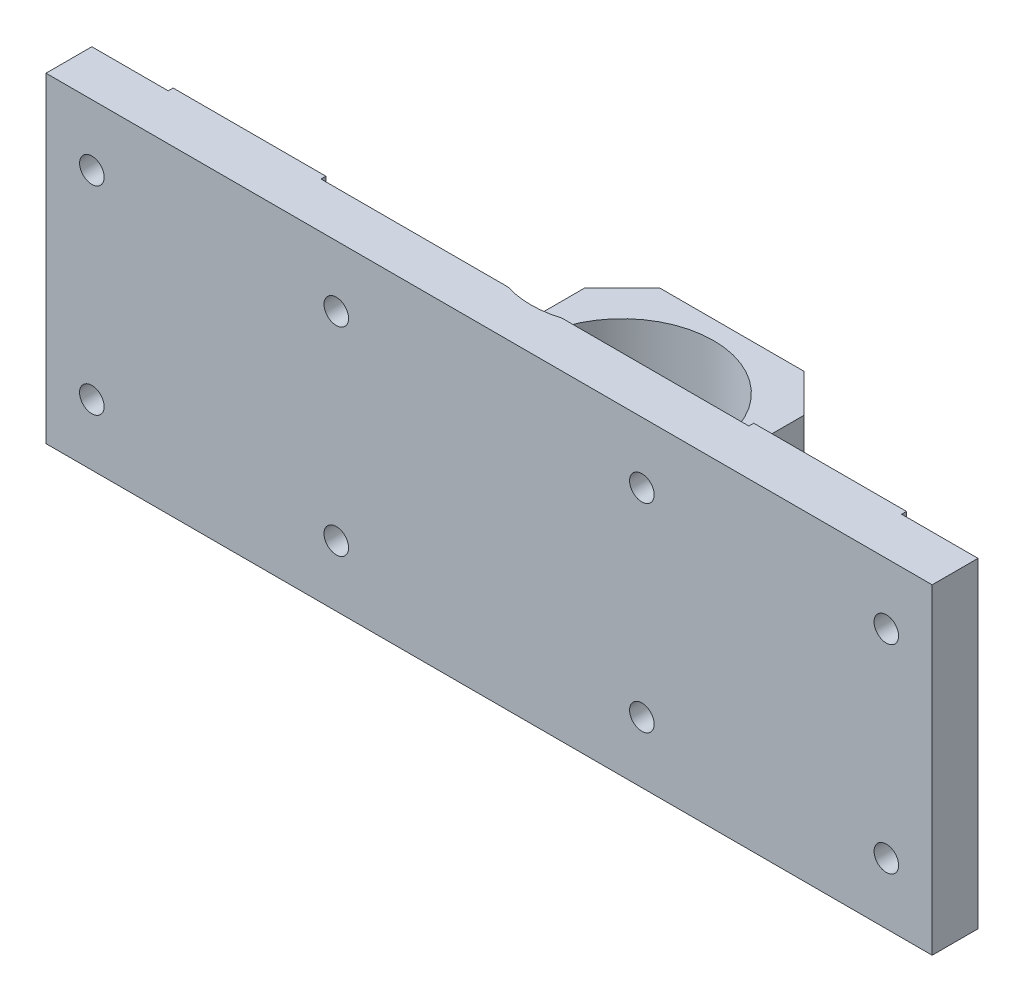
SolidWorks part; units mm, degrees
ref_plane "Front Plane" through (0, 0, 0) normal (0, 0, 1) x (1, 0, 0)
ref_plane "Top Plane" through (0, 0, 0) normal (0, 1, 0) x (1, 0, 0)
ref_plane "Right Plane" through (0, 0, 0) normal (1, 0, 0) x (0, 0, -1)
sketch "Sketch1" plane through (0, 0, 0) normal (0, 0, 1) x (1, 0, 0)
  line L1 (-87.7906, 37.622) -> (96.3594, 37.622)
  line L2 (-87.7906, 37.622) -> (-87.7906, -29.053)
  line L3 (-87.7906, -29.053) -> (96.3594, -29.053)
  line L4 (96.3594, 37.622) -> (96.3594, -29.053)
  dimension "D1" = 184.15
  dimension "D2" = 66.675
extrude "Boss-Extrude1" add sketch "Sketch1" along normal blind 9.525
sketch "Sketch5" plane through (0, 37.622, 0) normal (0, 1, 0) x (1, 0, 0)
  line L0 (10.8884, 0) -> (10.8884, -9.525)
  line L1 (96.3594, 0) -> (-87.7906, 0) construction
  line L2 (96.3594, -9.525) -> (-87.7906, -9.525) construction
  line L3 (-2.3196, 0) -> (-2.3196, -9.525)
  point P8 (4.2844, 0)
  dimension "D1" = 6.604
  dimension "D2" = 6.604
sketch "Sketch6" plane through (0, 37.622, 0) normal (0, 1, 0) x (1, 0, 0)
  arc A0 (10.8884, 0) -> (-2.3196, 0) centre (4.2844, 10.8827) cw
extrude "Cut-Extrude1" cut sketch "Sketch6" against normal through all and the other way through all flip side to cut
sketch "Sketch7" plane through (0, 37.622, 0) normal (0, 1, 0) x (1, 0, 0)
  line L0 (4.2844, -4.7215) -> (4.2844, 18.1385)
  line L1 (-87.7906, -9.525) -> (-87.7906, 0) construction
  circle A1 centre (4.2844, 18.1385) radius 22.8473
  dimension "D1" = 22.86
  dimension "D2" = 92.075
extrude "Boss-Extrude2" add sketch "Sketch7" against normal through all contours A1
sketch "Sketch8" plane through (0, 37.622, 0) normal (0, 1, 0) x (1, 0, 0)
  circle A0 centre (4.2844, 18.1385) radius 18.9865
  dimension "D1" = 37.973
extrude "Cut-Extrude2" cut sketch "Sketch8" against normal blind 61.595
sketch "Sketch9" plane through (0, -23.973, 0) normal (0, 1, 0) x (1, 0, 0)
  circle A0 centre (4.2844, 18.1385) radius 7.9375
  circle A1 centre (4.2844, 18.1385) radius 18.9865 construction
  dimension "D1" = 15.875
  dimension "D2" = 0
extrude "Cut-Extrude3" cut sketch "Sketch9" against normal through all
sketch "Sketch12" plane through (0, 37.622, 0) normal (0, 1, 0) x (1, 0, 0)
  line L0 (27.1317, 18.1385) -> (27.1317, 0)
  line L1 (96.3594, 0) -> (18.1766, 0) construction
  line L2 (27.1317, 0) -> (18.1766, 0)
  line L3 (-18.5629, 18.1385) -> (-18.5629, 0)
  line L4 (-9.6078, 0) -> (-87.7906, 0) construction
  line L5 (-18.5629, 0) -> (-9.6078, 0)
  circle A0 centre (4.2844, 18.1385) radius 22.8473 construction
  arc A1 (18.1766, 0) -> (27.1317, 18.1385) centre (4.2844, 18.1385) ccw
  arc A2 (-9.6078, 0) -> (-18.5629, 18.1385) centre (4.2844, 18.1385) cw
extrude "Boss-Extrude3" add sketch "Sketch12" against normal up to surface (66.675 mm away) up to face at (4.2844, -29.053, -10.201)
sketch "Sketch16" plane through (0, -29.053, 0) normal (0, -1, 0) x (1, 0, 0)
  line L0 (-18.5629, -18.1385) -> (-18.5629, -40.9857)
  line L1 (4.2844, -40.9857) -> (-18.5629, -40.9857)
  arc A0 (-18.5629, -18.1385) -> (27.1317, -18.1385) centre (4.2844, -18.1385) ccw construction
  arc A1 (-18.5629, -18.1385) -> (4.2844, -40.9857) centre (4.2844, -18.1385) ccw
extrude "Boss-Extrude4" add sketch "Sketch16" against normal up to surface (66.675 mm away) up to face at (4.2844, 37.622, -5.0093)
sketch "Sketch18" plane through (0, -29.053, 0) normal (0, -1, 0) x (1, 0, 0)
  line L0 (27.1317, -18.1385) -> (27.1317, -40.9857)
  line L1 (27.1317, -40.9857) -> (4.2844, -40.9857)
  arc A0 (27.1317, -18.1385) -> (4.2844, -40.9857) centre (4.2844, -18.1385) cw
extrude "Boss-Extrude5" add sketch "Sketch18" against normal up to surface (66.675 mm away) up to face at (4.8102, 37.622, -9.5324)
sketch "Sketch19" plane through (0, 37.622, 0) normal (0, 1, 0) x (1, 0, 0)
  line L2 (27.1317, 40.9857) -> (-18.5629, 40.9857) construction
  line L3 (19.2577, 40.9857) -> (27.1317, 40.9857)
  line L6 (-18.5629, 40.9857) -> (-18.5629, 0) construction
  line L8 (-18.5629, 40.9857) -> (-18.5629, 33.1259)
  line L9 (-18.5629, 33.1259) -> (-10.703, 40.9857)
  line L10 (-10.703, 40.9857) -> (-18.5629, 40.9857)
  line L11 (19.2577, 40.9857) -> (27.1317, 33.1117)
  line L12 (27.1317, 0) -> (27.1317, 40.9857) construction
  line L13 (27.1317, 33.1117) -> (27.1317, 40.9857)
  dimension "D1" = 7.8599
  dimension "D2" = 7.874
extrude "Cut-Extrude6" cut sketch "Sketch19" against normal through all
hole_wizard "#10 Clearance Hole1" positions "Sketch23" profile "Sketch24" hole size "#10" standard "ANSI Inch" end condition through all
sketch "Sketch23" plane through (0, 0, 0) normal (0, 0, -1) x (-1, 0, 0)
  line L0 (87.7906, 37.622) -> (87.7906, -29.053) construction
  line L1 (87.7906, -29.053) -> (18.5629, -29.053) construction
  line L2 (18.5629, 37.622) -> (87.7906, 37.622) construction
  line L3 (-96.3594, -29.053) -> (-96.3594, 37.622) construction
  line L4 (-96.3594, 37.622) -> (-27.1317, 37.622) construction
  line L5 (-27.1317, -29.053) -> (-96.3594, -29.053) construction
  point P0 (78.2656, 24.922)
  point P2 (78.2656, -16.353)
  point P4 (-86.8344, -16.353)
  point P6 (-86.8344, 24.922)
  dimension "D1" = 9.525
  dimension "D2" = 12.7
  dimension "D3" = 12.7
  dimension "D4" = 9.525
  dimension "D5" = 9.525
  dimension "D6" = 12.7
  dimension "D7" = 12.7
  dimension "D8" = 9.525
sketch "Sketch24" plane through (-78.2656, 24.922, 0) normal (1, 0, 0) x (0, 1, 0)
  line L0 (0, 0) -> (0, 9.525)
  line L1 (0, 9.525) -> (2.5527, 9.525)
  line L2 (2.5527, 9.525) -> (2.5527, 0)
  line L5 (2.5527, 0) -> (0, 0)
  line L11 (0, -6.35) -> (0, 107.95) construction
  dimension "Thru Hole Dia." = 5.1054
  dimension "Thru Hole Depth" = 9.525
hole_wizard "#10 Clearance Hole2" positions "Sketch25" profile "Sketch26" hole size "#10" standard "ANSI Inch" end condition through all
sketch "Sketch25" plane through (0, 0, 0) normal (0, 0, -1) x (-1, 0, 0)
  line L0 (87.7906, -29.053) -> (18.5629, -29.053) construction
  line L2 (18.5629, 37.622) -> (87.7906, 37.622) construction
  line L3 (-96.3594, 37.622) -> (-27.1317, 37.622) construction
  line L5 (-27.1317, -29.053) -> (-96.3594, -29.053) construction
  circle A0 centre (78.2656, -16.353) radius 2.5527 construction
  circle A1 centre (78.2656, 24.922) radius 2.5527 construction
  circle A2 centre (-86.8344, 24.922) radius 2.5527 construction
  circle A3 centre (-86.8344, -16.353) radius 2.5527 construction
  point P0 (27.4656, -16.353)
  point P2 (27.4656, 24.922)
  point P4 (-36.0344, 24.922)
  point P6 (-36.0344, -16.353)
  dimension "D1" = 12.7
  dimension "D2" = 50.8
  dimension "D3" = 50.8
  dimension "D4" = 12.7
  dimension "D5" = 12.7
  dimension "D6" = 50.8
  dimension "D7" = 50.8
  dimension "D8" = 12.7
sketch "Sketch26" plane through (-27.4656, -16.353, 0) normal (1, 0, 0) x (0, 1, 0)
  line L0 (0, 0) -> (0, 9.525)
  line L1 (0, 9.525) -> (2.5527, 9.525)
  line L2 (2.5527, 9.525) -> (2.5527, 0)
  line L5 (2.5527, 0) -> (0, 0)
  line L11 (0, -6.35) -> (0, 107.95) construction
  dimension "Thru Hole Dia." = 5.1054
  dimension "Thru Hole Depth" = 9.525
sketch "Sketch31" plane through (0, 0, -40.9857) normal (0, 0, -1) x (-1, 0, 0)
  line L1 (-19.2577, -29.053) -> (10.703, -29.053)
  line L2 (-19.2577, -29.053) -> (-19.2577, 37.622)
  line L3 (-19.2577, 37.622) -> (10.703, 37.622)
  line L4 (10.703, -29.053) -> (10.703, 37.622)
extrude "Boss-Extrude6" [suppressed] add sketch "Sketch31" along normal blind 2.54
hole_wizard "3/16 (0.1875) Diameter Hole3" positions "Sketch32" profile "Sketch33" hole size "3/16" standard "ANSI Inch" end condition up to next
sketch "Sketch32" plane through (-25.8444, 0, -25.8444) normal (-0.7071, 0, -0.7071) x (-0.7071, 0, 0.7071)
  line L0 (-10.2976, -29.053) -> (-21.4131, -29.053) construction
  line L1 (-10.2976, -29.053) -> (-10.2976, 37.622) construction
  point P0 (-15.3776, -20.163)
  point P2 (-15.3776, -7.463)
  dimension "D1" = 8.89
  dimension "D2" = 12.7
  dimension "D3" = 5.08
sketch "Sketch33" plane through (-14.9708, -20.163, -36.718) normal (0, 1, 0) x (-0.7071, 0, 0.7071)
  line L0 (0, 0) -> (0, 7.7726)
  line L1 (0, 7.7726) -> (2.3812, 7.7726)
  line L2 (2.3812, 7.7726) -> (2.3812, 0)
  line L5 (2.3812, 0) -> (0, 0)
  line L11 (0, -6.35) -> (0, 107.95) construction
  dimension "Thru Hole Dia." = 4.7625
  dimension "Thru Hole Depth" = 7.7726
hole_wizard "3/16 (0.1875) Diameter Hole4" positions "Sketch34" profile "Sketch35" hole size "3/16" standard "ANSI Inch" end condition up to next
sketch "Sketch34" plane through (30.1217, 0, -30.1217) normal (0.7071, 0, -0.7071) x (-0.7071, 0, -0.7071)
  line L0 (15.3641, -29.053) -> (4.2285, -29.053) construction
  line L1 (4.2285, -29.053) -> (4.2285, 37.622) construction
  point P0 (9.3085, -20.163)
  point P2 (9.3085, -7.463)
  dimension "D1" = 8.89
  dimension "D2" = 12.7
  dimension "D3" = 5.08
sketch "Sketch35" plane through (23.5395, -20.163, -36.7038) normal (0, 1, 0) x (-0.7071, 0, -0.7071)
  line L0 (0, 0) -> (0, 7.7629)
  line L1 (0, 7.7629) -> (2.3812, 7.7629)
  line L2 (2.3812, 7.7629) -> (2.3812, 0)
  line L5 (2.3812, 0) -> (0, 0)
  line L11 (0, -6.35) -> (0, 107.95) construction
  dimension "Thru Hole Dia." = 4.7625
  dimension "Thru Hole Depth" = 7.7629
sketch "Sketch36" plane through (0, 0, 0) normal (0, 0, -1) x (-1, 0, 0)
  line L0 (-96.3594, 37.622) -> (-27.1317, 37.622) construction
  line L1 (-80.4844, 37.622) -> (-48.7344, 37.622)
  line L2 (-80.4844, 37.622) -> (-80.4844, -29.053)
  line L3 (-80.4844, -29.053) -> (-48.7344, -29.053)
  line L4 (-48.7344, 37.622) -> (-48.7344, -29.053)
  line L5 (-27.1317, -29.053) -> (-96.3594, -29.053) construction
  line L6 (18.5629, 37.622) -> (87.7906, 37.622) construction
  line L7 (40.1656, 37.622) -> (71.9156, 37.622)
  line L8 (40.1656, 37.622) -> (40.1656, -29.053)
  line L9 (40.1656, -29.053) -> (71.9156, -29.053)
  line L10 (71.9156, 37.622) -> (71.9156, -29.053)
  line L11 (87.7906, -29.053) -> (18.5629, -29.053) construction
  line L12 (87.7906, 37.622) -> (87.7906, -29.053) construction
  line L13 (-96.3594, -29.053) -> (-96.3594, 37.622) construction
  dimension "D1" = 15.875
  dimension "D2" = 31.75
  dimension "D3" = 15.875
  dimension "D4" = 31.75
extrude "Boss-Extrude7" add sketch "Sketch36" along normal blind 1.016
ref_plane "Plane1" through (4.2844, 0, 0) normal (1, 0, 0) x (0, 0, -1)
sketch "Sketch37" plane through (27.1317, 0, 0) normal (1, 0, 0) x (0, 0, -1)
  line L0 (33.1117, -29.053) -> (0, -29.053) construction
  line L1 (5.4385, -29.053) -> (30.8385, -29.053)
  line L2 (5.4385, -29.053) -> (5.4385, -10.003)
  line L3 (5.4385, -10.003) -> (30.8385, -10.003)
  line L4 (30.8385, -29.053) -> (30.8385, -10.003)
  line L5 (18.1385, -23.973) -> (18.1385, 37.622) construction
  line L6 (18.1385, 37.622) -> (18.1385, -32.4273) construction
  line L7 (40.9857, 37.622) -> (-4.7088, 37.622) construction
  dimension "D1" = 25.4
  dimension "D2" = 19.05
extrude "Boss-Extrude8" add sketch "Sketch37" along normal blind 11.0998
sketch "Sketch38" plane through (0, -10.003, 0) normal (0, 1, 0) x (1, 0, 0)
  line L0 (27.1317, 30.8385) -> (27.1317, 5.4385) construction
  line L1 (27.1317, 11.2805) -> (34.2691, 11.2805)
  line L2 (27.1317, 11.2805) -> (27.1317, 24.9965)
  line L3 (27.1317, 24.9965) -> (34.2691, 24.9965)
  line L4 (34.2691, 11.2805) -> (34.2691, 24.9965)
  line L5 (38.2315, 18.1385) -> (23.3979, 18.1385) construction
  line L6 (38.2315, 30.8385) -> (38.2315, 5.4385) construction
  dimension "D1" = 13.716
  dimension "D2" = 7.1374
extrude "Cut-Extrude7" cut sketch "Sketch38" against normal blind 12.7
hole_wizard "1/4 Clearance Hole1" positions "Sketch39" profile "Sketch40" hole size "1/4" standard "ANSI Inch" end condition up to next
sketch "Sketch39" plane through (38.2315, 0, 0) normal (1, 0, 0) x (0, 0, -1)
  line L0 (18.1385, -10.003) -> (18.1385, -33.3111) construction
  line L1 (30.8385, -10.003) -> (5.4385, -10.003) construction
  point P0 (18.1385, -15.5529)
  dimension "D1" = 5.5499
sketch "Sketch40" plane through (38.2315, -15.5529, -18.1385) normal (0, 1, 0) x (0, 0, -1)
  line L0 (0, 0) -> (0, 56.7943)
  line L1 (0, 56.7943) -> (3.3782, 56.7943)
  line L2 (3.3782, 56.7943) -> (3.3782, 0)
  line L5 (3.3782, 0) -> (0, 0)
  line L11 (0, -6.35) -> (0, 107.95) construction
  dimension "Thru Hole Dia." = 6.7564
  dimension "Thru Hole Depth" = 56.7943
hole_wizard "13/64 (0.20313) Diameter Hole1" positions "Sketch41" profile "Sketch42" hole size "13/64" standard "ANSI Inch" end condition up to next
sketch "Sketch41" plane through (27.1317, 0, 0) normal (1, 0, 0) x (0, 0, -1)
  point P0 (18.1385, -15.5529)
sketch "Sketch42" plane through (27.1317, -15.5529, -18.1385) normal (0, 1, 0) x (0, 0, -1)
  line L0 (0, 0) -> (0, 45.6945)
  line L1 (0, 45.6945) -> (2.5798, 45.6945)
  line L2 (2.5798, 45.6945) -> (2.5798, 0)
  line L5 (2.5798, 0) -> (0, 0)
  line L11 (0, -6.35) -> (0, 107.95) construction
  dimension "Thru Hole Dia." = 5.1595
  dimension "Thru Hole Depth" = 45.6945
mirror "Mirror1" about plane through (4.2844, 0, 0) normal (1, 0, 0) of "13/64 (0.20313) Diameter Hole1", "Cut-Extrude7", "1/4 Clearance Hole1", "Boss-Extrude8"
fillet "Fillet1" radius 3.175 8 edges at (27.1317, -19.528, -5.4385) (38.2315, -19.528, -5.4385) (38.2315, -19.528, -30.8385) (27.1317, -19.528, -30.8385) (-29.6627, -19.528, -5.4385) (-18.5629, -19.528, -5.4385) (-29.6627, -19.528, -30.8385) (-18.5629, -19.528, -30.8385)
sketch "Sketch43" plane through (0, 37.622, 0) normal (0, 1, 0) x (1, 0, 0)
  line L0 (27.1317, 0) -> (-18.5629, 0)
  line L1 (27.1317, 0) -> (27.1317, 42.6742)
  line L2 (-18.5629, 0) -> (-18.5629, 42.6742)
  line L3 (27.1317, 42.6742) -> (-18.5629, 42.6742)
extrude "Cut-Extrude8" cut sketch "Sketch43" against normal blind 25.4
